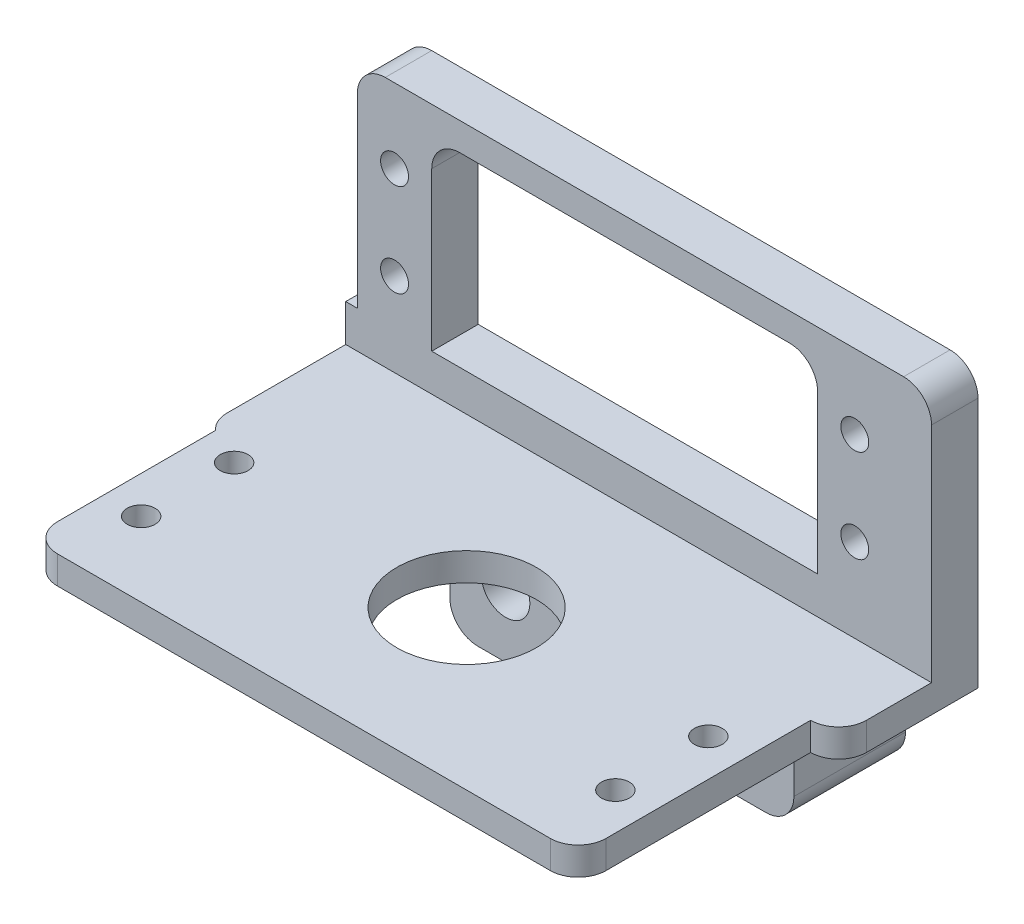
SolidWorks part; units mm, degrees
material "聚脂树脂"
ref_plane "前视基准面" through (0, 0, 0) normal (0, 0, 1) x (1, 0, 0)
ref_plane "上视基准面" through (0, 0, 0) normal (0, 1, 0) x (1, 0, 0)
ref_plane "右视基准面" through (0, 0, 0) normal (1, 0, 0) x (0, 0, -1)
other "Configuration Table"
sketch "草图1" plane through (0, 0, 0) normal (0, 1, 0) x (1, 0, 0)
  line L1 (-30, -2.5) -> (30, -2.5)
  line L2 (-30, -2.5) -> (-30, 2.5)
  line L3 (-30, 2.5) -> (30, 2.5)
  line L4 (30, -2.5) -> (30, 2.5)
  line L5 (-30, -2.5) -> (30, 2.5) construction
  line L6 (-30, 2.5) -> (30, -2.5) construction
  point P0 (0, 0)
  dimension "D1" = 60
  dimension "D2" = 5
extrude "凸台-拉伸1" add sketch "草图1" along normal blind 7
sketch "草图2" plane through (0, 7, 0) normal (0, 1, 0) x (1, 0, 0)
  line L0 (0, 0) -> (0, 33.932) construction
  line L1 (0, 0) -> (43.846, 0) construction
  line L6 (9.89, 0) -> (9.89, 32.9669) construction
  line L7 (20.75, -2.5) -> (28.75, -2.5)
  line L8 (20.75, -2.5) -> (20.75, 2.5)
  line L9 (20.75, 2.5) -> (28.75, 2.5)
  line L10 (28.75, -2.5) -> (28.75, 2.5)
  line L11 (20.75, -2.5) -> (28.75, 2.5) construction
  line L12 (20.75, 2.5) -> (28.75, -2.5) construction
  line L17 (-20.75, 2.5) -> (-28.75, -2.5) construction
  line L18 (-20.75, -2.5) -> (-28.75, 2.5) construction
  line L19 (-28.75, -2.5) -> (-28.75, 2.5)
  line L20 (-20.75, 2.5) -> (-28.75, 2.5)
  line L21 (-20.75, -2.5) -> (-20.75, 2.5)
  line L22 (-20.75, -2.5) -> (-28.75, -2.5)
  line L23 (30, 2.5) -> (-30, 2.5) construction
  point P3 (24.75, 0)
  point P15 (-24.75, 0)
  dimension "D1" = 9.89
  dimension "D2" = 49.5
  dimension "D3" = 5
  dimension "D4" = 0
  dimension "D5" = 8
extrude "凸台-拉伸2" add sketch "草图2" along normal blind 20
sketch "草图3" plane through (0, 0, -2.5) normal (0, 0, -1) x (-1, 0, 0)
  line L0 (-28.75, 17) -> (28.75, 17) construction
  line L1 (-28.75, 27) -> (-28.75, 7) construction
  line L2 (28.75, 27) -> (28.75, 7) construction
  line L3 (-20.75, 27) -> (-20.75, 7) construction
  line L4 (0, 0) -> (0, 27.0177) construction
  circle A0 centre (-24.75, 22) radius 1.5
  circle A1 centre (-24.75, 12) radius 1.5
  circle A2 centre (24.75, 12) radius 1.5
  circle A3 centre (24.75, 22) radius 1.5
  dimension "D1" = 3
  dimension "D2" = 3
  dimension "D3" = 10
  dimension "D4" = 5
  dimension "D5" = 4
  dimension "D6" = 4
extrude "切除-拉伸1" cut sketch "草图3" against normal blind 15
sketch "草图6" plane through (0, 0, 2.5) normal (0, 0, 1) x (1, 0, 0)
  line L0 (-30, 0) -> (-30, 3)
  line L1 (-30, 7) -> (-30, 0) construction
  line L2 (-30, 3) -> (30, 3)
  line L3 (30, 7) -> (30, 0) construction
  line L4 (30, 3) -> (30, 0)
  line L5 (30, 0) -> (-30, 0)
  dimension "D1" = 3
extrude "凸台-拉伸3" add sketch "草图6" along normal blind 35
sketch "草图7" plane through (0, 3, 0) normal (0, 1, 0) x (1, 0, 0)
  line L0 (-30, -17.5) -> (-29, -17.5)
  line L1 (-30, -37.5) -> (-30, -2.5) construction
  line L2 (-29, -17.5) -> (-29, -37.5)
  line L3 (30, -37.5) -> (-30, -37.5) construction
  line L4 (-29, -37.5) -> (-30, -37.5)
  line L5 (-30, -37.5) -> (-30, -17.5)
  dimension "D1" = 1
  dimension "D2" = 20
extrude "切除-拉伸2" cut sketch "草图7" against normal blind 40
sketch "草图8" plane through (0, 3, 0) normal (0, 1, 0) x (1, 0, 0)
  line L0 (30, -37.5) -> (-29, -37.5) construction
  line L1 (-30, -17.5) -> (-30, -2.5) construction
  circle A0 centre (-25, -19.5) radius 1.5
  circle A1 centre (-25, -29.5) radius 1.5
  circle A2 centre (26, -29.5) radius 1.5
  circle A3 centre (26, -19.5) radius 1.5
  circle A4 centre (1, -20.5) radius 7.5
  dimension "D1" = 3
  dimension "D2" = 3
  dimension "D3" = 3
  dimension "D4" = 3
  dimension "D5" = 15
  dimension "D6" = 17
  dimension "D7" = 31
extrude "切除-拉伸3" cut sketch "草图8" against normal blind 10
sketch "草图9" plane through (0, 0, -2.5) normal (0, 0, -1) x (-1, 0, 0)
  line L0 (-3.7, 0) -> (-3.7, 47.677) construction
  line L1 (-22.2, 0) -> (-10.2, 0)
  line L2 (-30, 0) -> (30, 0) construction
  line L3 (-10.2, 0) -> (-10.2, -14)
  line L4 (-10.2, -14) -> (-22.2, -14)
  line L5 (-22.2, -14) -> (-22.2, 0)
  line L6 (2.8, -14) -> (14.8, -14)
  line L7 (2.8, 0) -> (2.8, -14)
  line L8 (14.8, 0) -> (2.8, 0)
  line L9 (14.8, -14) -> (14.8, 0)
  line L10 (0, 0) -> (0, 42.2521) construction
  line L11 (-24.75, 22) -> (-24.75, 12)
  line L12 (-24.75, 17) -> (-10, 17)
  circle A0 centre (-16.2, -7.219) radius 2.5
  circle A1 centre (8.8, -7.219) radius 2.5
  line M14 (-30, 0) -> (30, 0)
  dimension "D4" = 5
  dimension "D5" = 25
  dimension "D6" = 6
  dimension "D1" = 12
  dimension "D2" = 14
  dimension "D3" = 6.5
  dimension "D7" = 3.7
  dimension "D8" = 14.75
extrude "凸台-拉伸4" add sketch "草图9" against normal blind 9 and the other way blind 3 contours L5 L4 L3 A0 M14 | L6 L9 L7 A1 M14 region at (-8.8, -0.1844, -2.5) region at (16.2, -0.1844, -2.5)
fillet "圆角3" radius 3 1 edges at (-30, 1.5, 17.5)
sketch "草图11" plane through (0, 0, 37.5) normal (0, 0, 1) x (1, 0, 0)
  line L0 (-14.8, 0) -> (-14.8, -14)
  line L1 (-14.8, -14) -> (-2.8, -14)
  line L4 (-2.8, -14) -> (-2.8, 0)
  line L5 (-29, 0) -> (30, 0) construction
  line L6 (-2.8, 0) -> (-14.8, 0)
  line L7 (10.2, -14) -> (22.2, -14)
  line L8 (22.2, -14) -> (22.2, 0)
  line L9 (22.2, 0) -> (10.2, 0)
  line L11 (10.2, 0) -> (10.2, -14)
  line L12 (22.2, -14) -> (22.2, 0) construction
  line L13 (10.2, -14) -> (22.2, -14) construction
  line L14 (10.2, 0) -> (10.2, -14) construction
  line L15 (-2.8, 0) -> (-2.8, -14) construction
  line L16 (-2.8, -14) -> (-14.8, -14) construction
  line L17 (-14.8, -14) -> (-14.8, 0) construction
  circle A0 centre (-8.8, -7.219) radius 2.5
  circle A1 centre (16.2, -7.219) radius 2.5
  dimension "D1" = 5
  dimension "D2" = 5
sketch "草图12" plane through (0, 27, 0) normal (0, 1, 0) x (1, 0, 0)
  line L0 (-28.75, 2.5) -> (28.75, 2.5)
  line L1 (28.75, 2.5) -> (28.75, -2.5)
  line L2 (28.75, -2.5) -> (-28.75, -2.5)
  line L3 (-28.75, -2.5) -> (-28.75, 2.5)
  line L4 (28.75, 2.5) -> (20.75, 2.5) construction
  dimension "D1" = 57.5
extrude "凸台-拉伸6" add sketch "草图12" along normal blind 3
fillet "圆角6" radius 3 3 edges at (-20.75, 27, 0) (20.75, 27, 0) (-28.75, 30, 0)
fillet "圆角7" radius 1.5 4 edges at (-8.8, 0, -5.5) (16.2, 0, -5.5) (16.2, 0, -2.5) (-8.8, 0, -2.5)
fillet "圆角8" radius 5 4 edges at (-14.8, 0, 2) (-2.8, 0, 2) (10.2, 0, 2) (22.2, 0, 2)
fillet "圆角9" radius 3 4 edges at (-14.8, -14, 0.5) (-2.8, -14, 0.5) (10.2, -14, 0.5) (22.2, -14, 0.5)
fillet "圆角10" radius 3 2 edges at (-29, 1.5, 37.5) (30, 1.5, 37.5)
sketch "草图14" plane through (0, 7, 0) normal (0, 1, 0) x (1, 0, 0)
  line L4 (28.75, 2.5) -> (28.75, -2.5)
  line L5 (28.75, -2.5) -> (30, -2.5)
  line L6 (30, -2.5) -> (30, 2.5)
  line L7 (30, 2.5) -> (28.75, 2.5)
  line L8 (28.75, 2.5) -> (28.75, -2.5)
  line L9 (28.75, -2.5) -> (30, -2.5)
  line L10 (30, -2.5) -> (30, 2.5)
  line L11 (30, 2.5) -> (28.75, 2.5)
  dimension "D1" = 0
extrude "凸台-拉伸7" add sketch "草图14" along normal up to surface (23 mm away) up to face at (1.5, 30, 0)
sketch "草图16" plane through (30, 0, 0) normal (1, 0, 0) x (0, 0, -1)
  line L0 (-12.5, 0) -> (-12.5, 3)
  line L1 (-34.5, 0) -> (2.5, 0) construction
  line L2 (-34.5, 3) -> (-2.5, 3) construction
  line L3 (-12.5, 3) -> (-2.5, 3)
  line L4 (-2.5, 3) -> (-2.5, 30)
  line L5 (-2.5, 30) -> (2.5, 30)
  line L6 (2.5, 30) -> (2.5, 0)
  line L7 (2.5, -5) -> (2.5, 1.5) construction
  line L8 (2.5, 0) -> (-12.5, 0)
  dimension "D1" = 10
extrude "凸台-拉伸8" add sketch "草图16" along normal blind 3
fillet "圆角12" radius 3 2 edges at (33, 1.5, 12.5) (33, 30, 0)
sketch "草图17" plane through (0, 0, -5.5) normal (0, 0, -1) x (-1, 0, 0)
  circle A0 centre (-16.2, -7.219) radius 2.6
  circle A1 centre (8.8, -7.219) radius 2.6
  dimension "D1" = 5.2
  dimension "D2" = 5.2
extrude "切除-拉伸4" cut sketch "草图17" against normal blind 15
